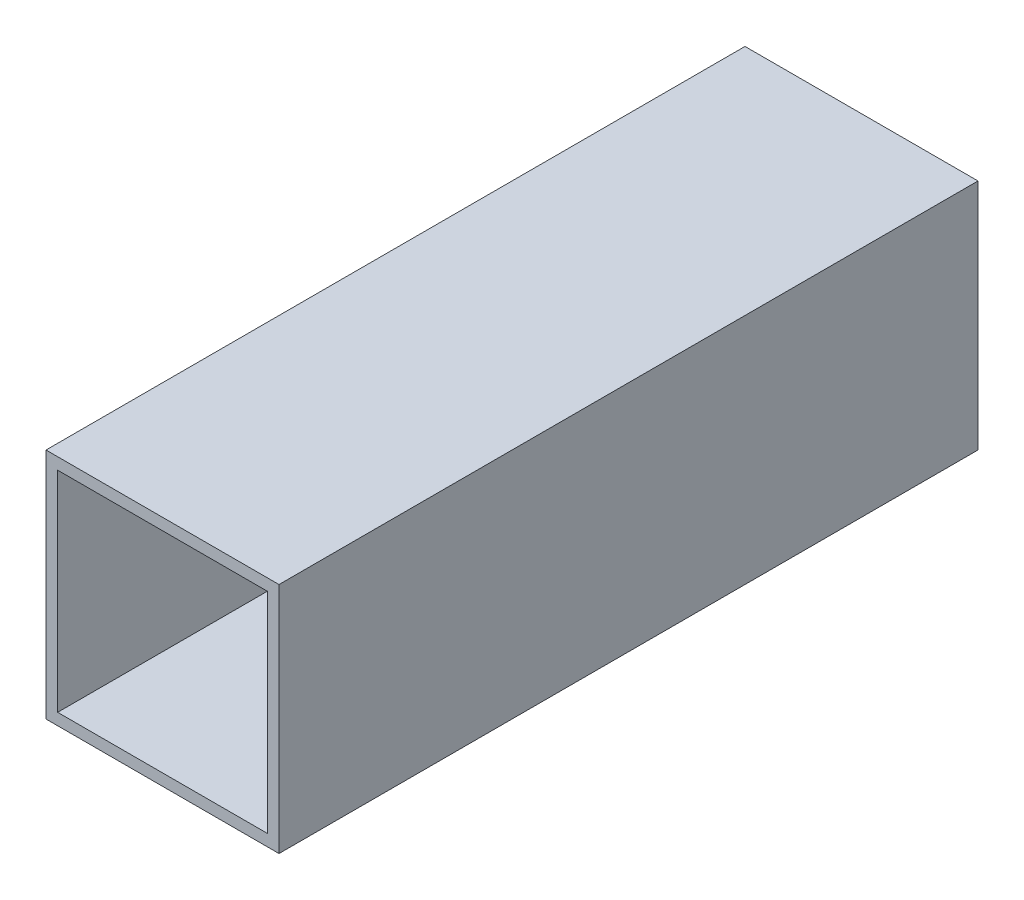
SolidWorks part; units mm, degrees
material "Glass"
ref_plane "Front Plane" through (0, 0, 0) normal (0, 0, 1) x (1, 0, 0)
ref_plane "Top Plane" through (0, 0, 0) normal (0, 1, 0) x (1, 0, 0)
ref_plane "Right Plane" through (0, 0, 0) normal (1, 0, 0) x (0, 0, -1)
sketch "Sketch1" plane through (0, 0, 0) normal (0, 0, 1) x (1, 0, 0)
  line L1 (1.6329, 0) -> (52.4329, 0)
  line L2 (1.6329, 0) -> (1.6329, 50.8)
  line L3 (1.6329, 50.8) -> (52.4329, 50.8)
  line L4 (52.4329, 0) -> (52.4329, 50.8)
  line L5 (4.1729, 2.54) -> (49.8929, 2.54)
  line L6 (4.1729, 2.54) -> (4.1729, 48.26)
  line L7 (4.1729, 48.26) -> (49.8929, 48.26)
  line L8 (49.8929, 2.54) -> (49.8929, 48.26)
  dimension "D1" = 50.8
  dimension "D2" = 50.8
  dimension "D3" = 45.72
  dimension "D4" = 45.72
  dimension "D5" = 2.54
  dimension "D6" = 2.54
extrude "Boss-Extrude1" add sketch "Sketch1" along normal blind 152.4
